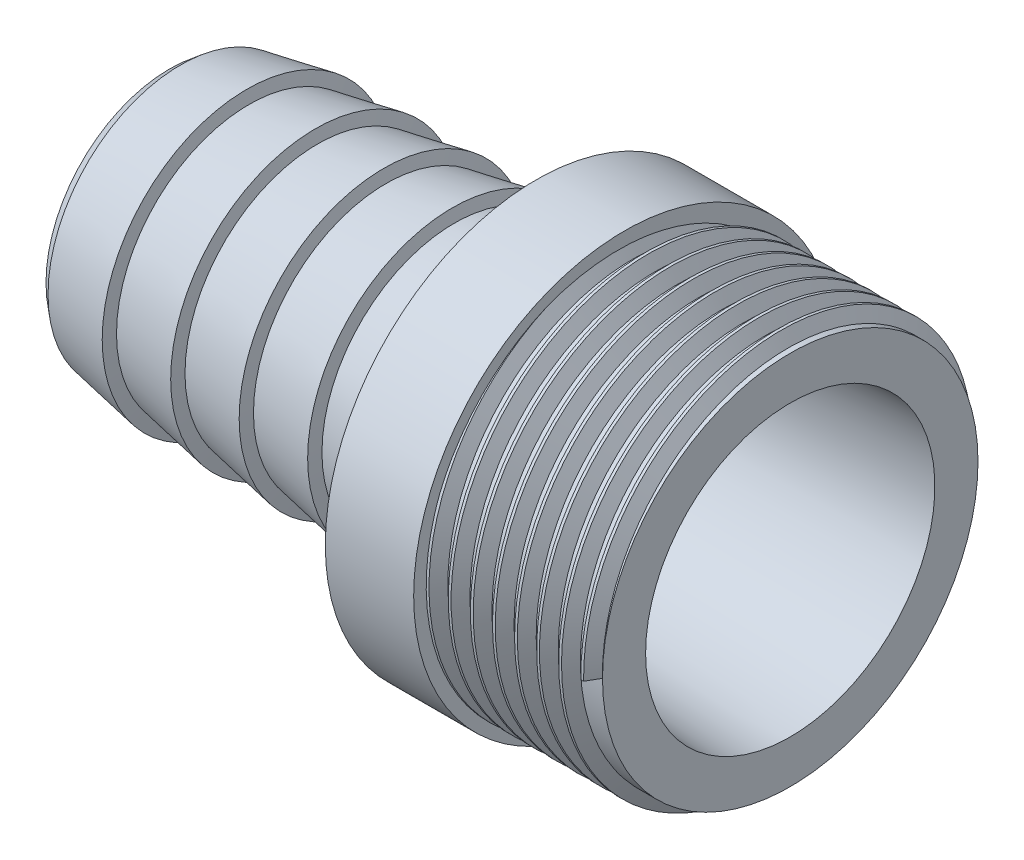
SolidWorks part; units mm, degrees
ref_plane "Front Plane" through (0, 0, 0) normal (0, 0, 1) x (1, 0, 0)
ref_plane "Top Plane" through (0, 0, 0) normal (0, 1, 0) x (1, 0, 0)
ref_plane "Right Plane" through (0, 0, 0) normal (1, 0, 0) x (0, 0, -1)
sketch "Sketch1" plane through (0, 0, 0) normal (0, 1, 0) x (1, 0, 0)
  line L0 (0, 0) -> (61.4833, 0) construction
  line L2 (-5.2397, 13.0954) -> (56.2, 13.0954) construction
  line L3 (0, 10.0954) -> (0, 11.1836)
  line L4 (0, 11.1836) -> (1, 12)
  line L5 (1, 12) -> (7, 13.0954)
  line L6 (1, 12) -> (53.9438, 12) construction
  line L7 (7, 13.0954) -> (7.2, 12)
  line L14 (7.2, 12) -> (13.2, 13.0954)
  line L22 (13.2, 13.0954) -> (13.4, 12)
  line L23 (13.4, 12) -> (19.4, 13.0954)
  line L24 (19.4, 13.0954) -> (19.6, 12)
  line L25 (19.6, 12) -> (25.6, 13.0954)
  line L26 (25.6, 13.0954) -> (25.8, 12)
  line L27 (25.8, 12) -> (31.8, 13.0954)
  line L28 (31.8, 13.0954) -> (33.2, 13.0954)
  line L29 (31.8, 13.0954) -> (32, 12) [skipped]
  line L30 (33.2, 13.0954) -> (33.2, 19.0954)
  line L31 (33.2, 19.0954) -> (41.2, 19.0954)
  line L39 (0, 12) -> (53.9438, 12) construction
  line L40 (-5.2397, 17) -> (56.2, 17) construction
  line L43 (41.2, 19.0954) -> (41.2, 17)
  line L44 (41.2, 17) -> (56.2, 17)
  line L45 (56.2, 17) -> (56.2, 13.0954)
  line L46 (56.2, 13.0954) -> (0, 10.0954)
  point P17 (56.2, 13.0954)
  dimension "D2" = 17
  dimension "D3" = 12
  dimension "D4" = 15
  dimension "D5" = 6
  dimension "D6" = 1
  dimension "D7" = 0.2
  dimension "D9" = 6
  dimension "D10" = 1.4
  dimension "D11" = 8
  dimension "D8" = 5
revolve "Revolve2" add sketch "Sketch1" angle 360 about L0
sketch "Sketch2" plane through (41.2, 0, 0) normal (1, 0, 0) x (0, 0, -1)
  circle A0 centre (0, 0) radius 13.0954
thread "Thread1" pitch 2 method extrude profile "Thread Profile2" start angle 0, offset 0, length 15, pitch 2, diameter 34
ref_plane "Plane2" through (56.2, 0, 17) normal (0, -1, 0) x (0, 0, 1)
sketch "Thread Profile2" plane through (56.2, 0, 17) normal (0, -1, 0) x (0, 0, 1)
  line L0 (0, 0) -> (0, 2) construction
  line L1 (0, 0) -> (1.0825, 0.625)
  line L2 (1.0825, 0.625) -> (1.0825, 0.875)
  line L3 (1.0825, 0.875) -> (0, 1.5)
  line L4 (1.0825, 0.75) -> (0, 0.75) construction
  line L11 (0, 0) -> (0, 1.5)
  point P2 (0, 0)
  dimension "Pitch" = 2
  dimension "Profile_Angle" = 60
  dimension "Profile_Land" = 0.25
  dimension "Profile_Height" = 1.0825
